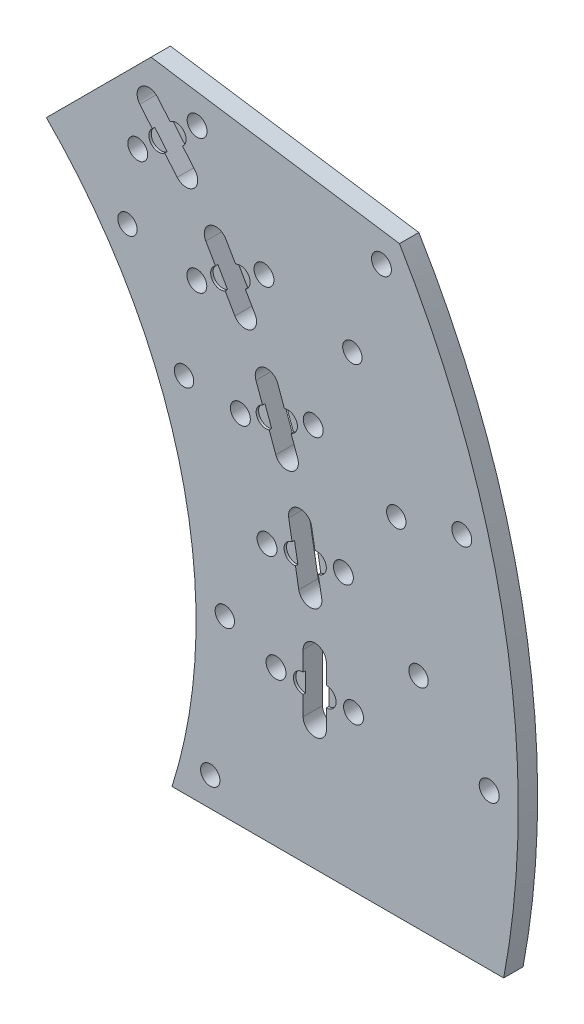
SolidWorks part; units mm, degrees
ref_plane "Front Plane" through (0, 0, 0) normal (0, 0, 1) x (1, 0, 0)
ref_plane "Top Plane" through (0, 0, 0) normal (0, 1, 0) x (1, 0, 0)
ref_plane "Right Plane" through (0, 0, 0) normal (1, 0, 0) x (0, 0, -1)
sketch "Sketch1" plane through (0, 0, 0) normal (0, 0, 1) x (1, 0, 0)
  line L0 (0, 0) -> (177.8, 0) construction
  line L1 (176.8984, 6.1774) -> (0, 0) construction
  line L2 (0, 0) -> (121.7947, 121.7947) construction
  line L3 (121.7947, 121.7947) -> (122.9173, 122.9173) construction
  line L4 (144.995, 101.5266) -> (0, 0) construction
  line L5 (0, 0) -> (163.5325, 67.7374) construction
  line L6 (167.4812, 0) -> (167.4812, -50.8) construction
  line L8 (159.5911, -50.8) -> (167.4812, -50.8) construction
  line L9 (172.1267, -41.275) -> (0, 0) construction
  line L10 (159.5911, -50.8) -> (268.2828, -50.8)
  line L11 (118.4271, 118.4271) -> (152.7152, 152.7152)
  line L12 (177.8, 0) -> (193.675, 0) construction
  line L13 (202.565, 0) -> (210.185, 0) construction
  line L14 (210.185, 0) -> (219.075, 0) construction
  line L15 (193.675, 0) -> (202.565, 0) construction
  line L16 (202.565, 0) -> (202.565, 9.525)
  line L17 (202.565, 0) -> (202.565, -9.525)
  line L18 (210.185, 9.525) -> (210.185, 0)
  line L19 (210.185, 0) -> (210.185, -9.525)
  line L20 (202.565, -9.525) -> (210.185, -9.525) construction
  line L21 (202.565, 9.525) -> (210.185, 9.525) construction
  line L22 (210.185, 9.525) -> (219.075, 0) construction
  line L23 (202.565, 9.525) -> (193.675, 0) construction
  line L24 (199.4876, 35.175) -> (201.1416, 25.7947)
  line L25 (199.4876, 35.175) -> (197.8336, 44.5553)
  line L26 (205.3378, 45.8785) -> (206.9918, 36.4982)
  line L27 (206.9918, 36.4982) -> (208.6458, 27.1179)
  line L28 (190.3488, 69.2813) -> (193.6066, 60.3307)
  line L29 (190.3488, 69.2813) -> (187.0911, 78.2319)
  line L30 (194.2516, 80.8381) -> (197.5093, 71.8875)
  line L31 (197.5093, 71.8875) -> (200.767, 62.9369)
  line L32 (175.4264, 101.2825) -> (180.1889, 93.0336)
  line L33 (175.4264, 101.2825) -> (170.6639, 109.5314)
  line L34 (177.263, 113.3414) -> (182.0255, 105.0925)
  line L35 (182.0255, 105.0925) -> (186.788, 96.8436)
  line L36 (155.1738, 130.2063) -> (161.2963, 122.9097)
  line L37 (155.1738, 130.2063) -> (149.0512, 137.5028)
  line L38 (154.8885, 142.4009) -> (161.0111, 135.1043)
  line L39 (161.0111, 135.1043) -> (167.1336, 127.8077)
  line L40 (0, 0) -> (193.675, 0) construction
  line L41 (0, 0) -> (190.7326, 33.6313) construction
  line L42 (0, 0) -> (254, 0) construction
  line L43 (254, 0) -> (263.525, 0) construction
  line L44 (254.5456, 68.2053) -> (0, 0) construction
  line L45 (152.7152, 152.7152) -> (234.123, 140.5088)
  line L46 (167.8212, 140.8187) -> (228.2193, 131.7625) construction
  line L47 (254.5456, 68.2053) -> (263.746, 70.6705) construction
  line L48 (0, 0) -> (240.3818, 21.0307) construction
  line L49 (0, 0) -> (240.3818, 21.0307) construction
  line L50 (0, 0) -> (233.0779, 62.453) construction
  arc A0 (172.2437, 0) -> (121.7947, 121.7947) centre (0, 0) ccw construction
  arc A1 (173.8312, 0) -> (122.9173, 122.9173) centre (0, 0) ccw construction
  circle A2 centre (176.8984, 6.1774) radius 3.175
  circle A3 centre (144.995, 101.5266) radius 3.175
  circle A4 centre (163.5325, 67.7374) radius 3.175
  arc A5 (167.4812, 0) -> (118.4271, 118.4271) centre (0, 0) ccw
  arc A6 (167.4812, 0) -> (159.5911, -50.8) centre (0, 0) cw
  arc A7 (173.8312, 0) -> (166.2428, -50.8) centre (0, 0) cw construction
  circle A8 centre (172.1267, -41.275) radius 3.175
  circle A9 centre (193.675, 0) radius 9.525 construction
  circle A10 centre (219.075, 0) radius 9.525 construction
  arc A11 (202.565, -9.525) -> (210.185, -9.525) centre (206.375, -9.525) ccw
  arc A12 (202.565, 9.525) -> (210.185, 9.525) centre (206.375, 9.525) cw
  circle A13 centre (193.675, 0) radius 3.2639
  circle A14 centre (219.075, 0) radius 3.2639
  circle A15 centre (215.7468, 38.042) radius 3.2639
  arc A16 (201.1416, 25.7947) -> (208.6458, 27.1179) centre (204.8937, 26.4563) ccw
  arc A17 (197.8336, 44.5553) -> (205.3378, 45.8785) centre (201.5857, 45.2169) cw
  circle A18 centre (190.7326, 33.6313) radius 3.2639
  circle A19 centre (205.8632, 74.9281) radius 3.2639
  arc A20 (193.6066, 60.3307) -> (200.767, 62.9369) centre (197.1868, 61.6338) ccw
  arc A21 (187.0911, 78.2319) -> (194.2516, 80.8381) centre (190.6713, 79.535) cw
  circle A22 centre (181.995, 66.2408) radius 3.2639
  circle A23 centre (189.7245, 109.5375) radius 3.2639
  arc A24 (180.1889, 93.0336) -> (186.788, 96.8436) centre (183.4885, 94.9386) ccw
  arc A25 (170.6639, 109.5314) -> (177.263, 113.3414) centre (173.9635, 111.4364) cw
  circle A26 centre (167.7275, 96.8375) radius 3.2639
  circle A27 centre (167.8212, 140.8187) radius 3.2639
  arc A28 (161.2963, 122.9097) -> (167.1336, 127.8077) centre (164.215, 125.3587) ccw
  arc A29 (149.0512, 137.5028) -> (154.8885, 142.4009) centre (151.9699, 139.9519) cw
  circle A30 centre (148.3637, 124.4919) radius 3.2639
  circle A31 centre (263.525, 0) radius 3.2639
  circle A32 centre (254.5456, 68.2053) radius 3.2639
  circle A33 centre (228.2193, 131.7625) radius 3.2639
  arc A34 (234.123, 140.5088) -> (268.2828, -50.8) centre (0, 0) cw
  circle A36 centre (240.3818, 21.0307) radius 3.175
  circle A37 centre (233.0779, 62.453) radius 3.175
  circle A38 centre (218.6921, 101.9778) radius 3.175
  point P3 (172.2437, 0)
  point P96 (0, 0)
  dimension "D3" = 1.5875
  dimension "D4" = 6.35
  dimension "D5" = 2
  dimension "D7" = 10
  dimension "D8" = 6.35
  dimension "D9" = 6.35
  dimension "D11" = 6.35
  dimension "D13" = 6.35
  dimension "D15" = 19.05
  dimension "D16" = 7.62
  dimension "D17" = 19.05
  dimension "D21" = 15.875
  dimension "D22" = 6.5278
  dimension "D23" = 6.5278
  dimension "D28" = 6.5278
  dimension "D32" = 9.525
  dimension "D33" = 5
  dimension "D34" = 241.3
  dimension "D35" = 6.35
  dimension "D1" = 177.8
  dimension "D2" = 5.5562
  dimension "D6" = 45
  dimension "D10" = 22.5
  dimension "D12" = 50.8
  dimension "D14" = 9.525
  dimension "D18" = 9.525
  dimension "D19" = 9.525
  dimension "D20" = 25.4
  dimension "D25" = 10
  dimension "D26" = 254
  dimension "D27" = 9.525
  dimension "D30" = 15
  dimension "D31" = 9.525
  dimension "D37" = 10
  dimension "D24" = 5
  dimension "D29" = 3
  dimension "D36" = 3
extrude "Boss-Extrude1" add sketch "Sketch1" along normal blind 6.35 contours A34 L45 L11 A5 A6 L10 A33 A32 A31 A30 A27 A26 A23 A22 A19 A18 A15 A14 A13 A8 A4 A3 A2 L16 A12 L18 L19 A11 L17 L25 A17 L26 region at (207.9736, 48.0018, 0)
sketch "Sketch2" plane through (0, 0, 6.35) normal (0, 0, 1) x (1, 0, 0)
  line L0 (202.565, -9.525) -> (202.565, 9.525) construction
  line L1 (210.185, 9.525) -> (210.185, -9.525) construction
  line L2 (0, 0) -> (202.565, 0) construction
  line L3 (0, 0) -> (199.4876, 35.175) construction
  circle A0 centre (202.565, 0) radius 3.175
  circle A1 centre (210.185, 0) radius 3.175
  circle A2 centre (199.4876, 35.175) radius 3.175
  circle A3 centre (206.9918, 36.4982) radius 3.175
  circle A4 centre (190.3488, 69.2813) radius 3.175
  circle A5 centre (197.5093, 71.8875) radius 3.175
  circle A6 centre (175.4264, 101.2825) radius 3.175
  circle A7 centre (182.0255, 105.0925) radius 3.175
  circle A8 centre (155.1738, 130.2063) radius 3.175
  circle A9 centre (161.0111, 135.1043) radius 3.175
  dimension "D1" = 6.35
  dimension "D2" = 6.35
  dimension "D4" = 10
  dimension "D3" = 5
extrude "Cut-Extrude1" cut sketch "Sketch2" against normal blind 0.7937
